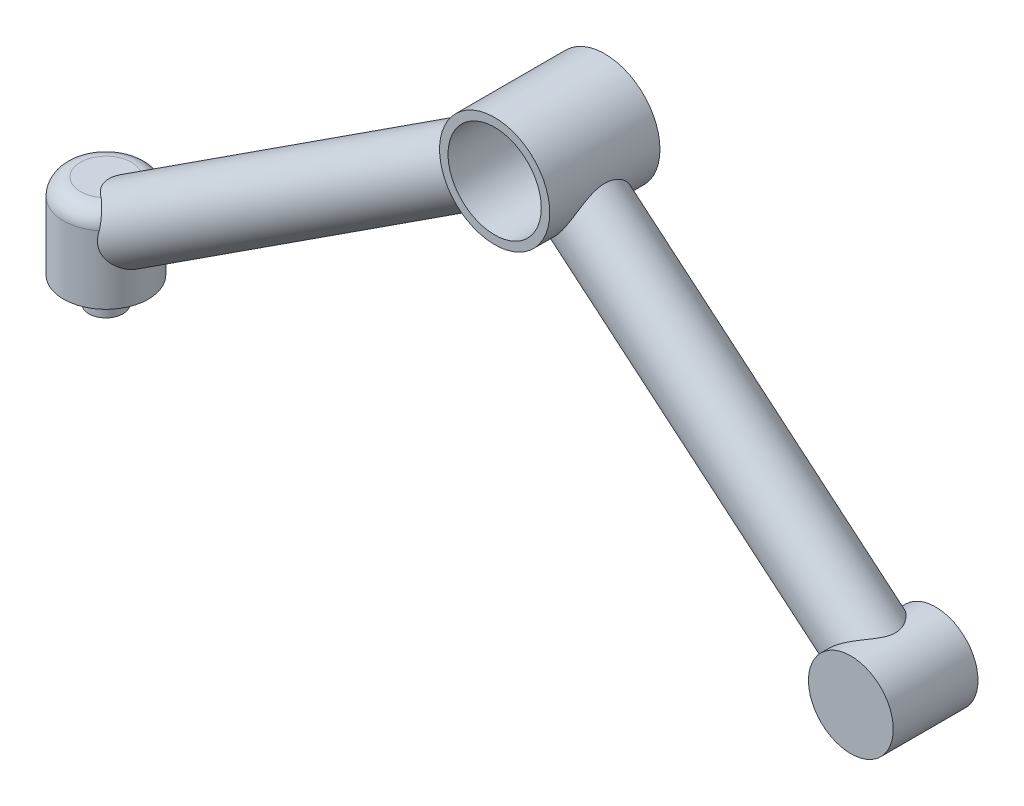
SolidWorks part; units mm, degrees
ref_plane "Front Plane" through (0, 0, 0) normal (0, 0, 1) x (1, 0, 0)
ref_plane "Top Plane" through (0, 0, 0) normal (0, 1, 0) x (1, 0, 0)
ref_plane "Right Plane" through (0, 0, 0) normal (1, 0, 0) x (0, 0, -1)
sketch "Sketch1" plane through (0, 0, 0) normal (0, 0, 1) x (1, 0, 0)
  line L0 (0, 0) -> (-261.777, -170) construction
  line L1 (0, 0) -> (202.5981, -170) construction
  line L2 (202.5981, -170) -> (202.5981, -64.2604) construction
  line L3 (-261.777, -170) -> (-261.777, -270) construction
  line L4 (202.5981, -170) -> (438.223, -170) construction
  line L5 (202.5981, -170) -> (91.5369, -270) construction
  line L6 (-286.777, -145) -> (-286.777, -195) construction
  line L7 (438.223, -170) -> (438.223, -270) construction
  line L8 (-236.777, -145) -> (-236.777, -195) construction
  line L9 (-286.777, -195) -> (-236.777, -195) construction
  line L10 (-236.777, -145) -> (-286.777, -145) construction
  line L11 (-261.777, -570) -> (438.223, -570) construction
  line L12 (-261.777, -670) -> (91.5369, -670) construction
  circle A0 centre (-261.777, -270) radius 50 construction
  circle A1 centre (-261.777, -270) radius 40 construction
  circle A2 centre (91.5369, -270) radius 40 construction
  circle A3 centre (91.5369, -270) radius 50 construction
  circle A4 centre (438.223, -270) radius 40 construction
  circle A5 centre (438.223, -270) radius 50 construction
  circle A6 centre (0, 0) radius 32.5 construction
  circle A7 centre (202.5981, -170) radius 25 construction
  point P13 (-286.777, -170)
  dimension "D7" = 80
  dimension "D8" = 100
  dimension "D13" = 65
  dimension "D14" = 50
  dimension "D1" = 50
  dimension "D2" = 107
  dimension "D3" = 170
  dimension "D4" = 100
  dimension "D5" = 48
  dimension "D6" = 700
  dimension "D9" = 25
  dimension "D10" = 50
  dimension "D11" = 400
  dimension "D12" = 100
sketch "Sketch2" plane through (0, 0, 0) normal (0, 0, 1) x (1, 0, 0)
  circle A0 centre (202.5981, -170) radius 25
  circle A1 centre (202.5981, -170) radius 25 construction
extrude "Boss-Extrude1" add sketch "Sketch2" along normal mid plane 50
sketch "Sketch3" plane through (0, 0, 0) normal (0, 0, 1) x (1, 0, 0)
  line L0 (-261.777, -195) -> (-261.777, -145) construction
  line L1 (-286.777, -195) -> (-236.777, -195) construction
  line L2 (-236.777, -145) -> (-286.777, -145) construction
  line L3 (-236.777, -155) -> (-236.777, -195)
  line L4 (-236.777, -195) -> (-261.777, -195)
  line L5 (-246.777, -145) -> (-261.777, -145)
  line L6 (-261.777, -195) -> (-261.777, -145)
  arc A0 (-236.777, -155) -> (-246.777, -145) centre (-246.777, -155) ccw
  point P12 (-236.777, -145)
  dimension "D1" = 10
revolve "Revolve1" add sketch "Sketch3" angle 360 about L0
sketch "Sketch4" plane through (0, 0, 0) normal (0, 0, 1) x (1, 0, 0)
  circle A0 centre (0, 0) radius 32.5
  circle A1 centre (0, 0) radius 32.5 construction
  circle A2 centre (0, 0) radius 27.5
  dimension "D1" = 55
extrude "Boss-Extrude2" add sketch "Sketch4" along normal mid plane 65 separate body
sketch "Sketch5" plane through (0, 0, 0) normal (0, 0, 1) x (1, 0, 0)
  line L0 (-261.777, -170) -> (-220.1413, -142.9614)
  line L1 (0, 0) -> (-261.777, -170) construction
sweep "Cut-Sweep1" cut path "Sketch5" circular profile diameter 40 parameters "D3"=40
sketch "Sketch14" plane through (0, 0, 0) normal (0, 0, 1) x (1, 0, 0)
  line L0 (-149.8134, -97.29) -> (-71.8587, -46.6656)
  line L1 (0, 0) -> (-261.777, -170) construction
sweep "Sweep1" add path "Sketch14" circular profile diameter 40 parameters "D3"=40
sweep "Cut-Sweep2" cut path "Sketch14<2>" circular profile diameter 30 parameters "D3"=30
sketch "Sketch14<2>" plane through (0, 0, 0) normal (0, 0, 1) x (1, 0, 0) same geometry as "Sketch14"
sketch "Sketch39" plane through (-149.8134, -97.29, 0) normal (-0.8387, -0.5446, 0) x (0, 0, 1)
  circle A0 centre (0, 0) radius 15 construction
  circle A1 centre (0, 0) radius 20
  circle A2 centre (0, 0) radius 20
  circle A3 centre (0, 0) radius 15
  dimension "D1" = 0
extrude "Boss-Extrude3" add sketch "Sketch39" along normal up to next
sketch "Sketch40" plane through (-71.8587, -46.6656, 0) normal (0.8387, 0.5446, 0) x (0, 0, -1)
  circle A0 centre (0, 0) radius 15 construction
  circle A1 centre (0, 0) radius 20
  circle A2 centre (0, 0) radius 20
  circle A3 centre (0, 0) radius 15
  dimension "D1" = 0
extrude "Boss-Extrude4" add sketch "Sketch40" along normal up to next
sketch "Sketch41" plane through (0, 0, 0) normal (0, 0, 1) x (1, 0, 0)
  line L0 (63.6127, -53.3774) -> (112.4695, -94.3731)
  line L1 (0, 0) -> (202.5981, -170) construction
sweep "Sweep2" add path "Sketch41" circular profile diameter 40 parameters "D3"=40
sweep "Cut-Sweep3" cut path "Sketch41<2>" circular profile diameter 30 parameters "D3"=30
sketch "Sketch41<2>" plane through (0, 0, 0) normal (0, 0, 1) x (1, 0, 0) same geometry as "Sketch41"
sketch "Sketch62" plane through (63.6127, -53.3774, 0) normal (-0.766, 0.6428, 0) x (0, 0, 1)
  circle A0 centre (0, 0) radius 15 construction
  circle A1 centre (0, 0) radius 20
  circle A2 centre (0, 0) radius 20
  circle A3 centre (0, 0) radius 15
  dimension "D1" = 0
extrude "Boss-Extrude5" add sketch "Sketch62" along normal up to next
sketch "Sketch63" plane through (112.4695, -94.3731, 0) normal (0.766, -0.6428, 0) x (0, 0, -1)
  circle A0 centre (0, 0) radius 15 construction
  circle A1 centre (0, 0) radius 20
  circle A2 centre (0, 0) radius 20
  circle A3 centre (0, 0) radius 15
  dimension "D1" = 0
extrude "Boss-Extrude6" add sketch "Sketch63" along normal up to next
sketch "Sketch64" plane through (0, -195, 0) normal (0, -1, 0) x (1, 0, 0)
  line L0 (-236.777, 0) -> (-286.777, 0) construction
  circle A0 centre (-261.777, 0) radius 10
  circle A1 centre (-261.777, 0) radius 25 construction
  dimension "D1" = 20
extrude "Boss-Extrude7" add sketch "Sketch64" along normal blind 15
